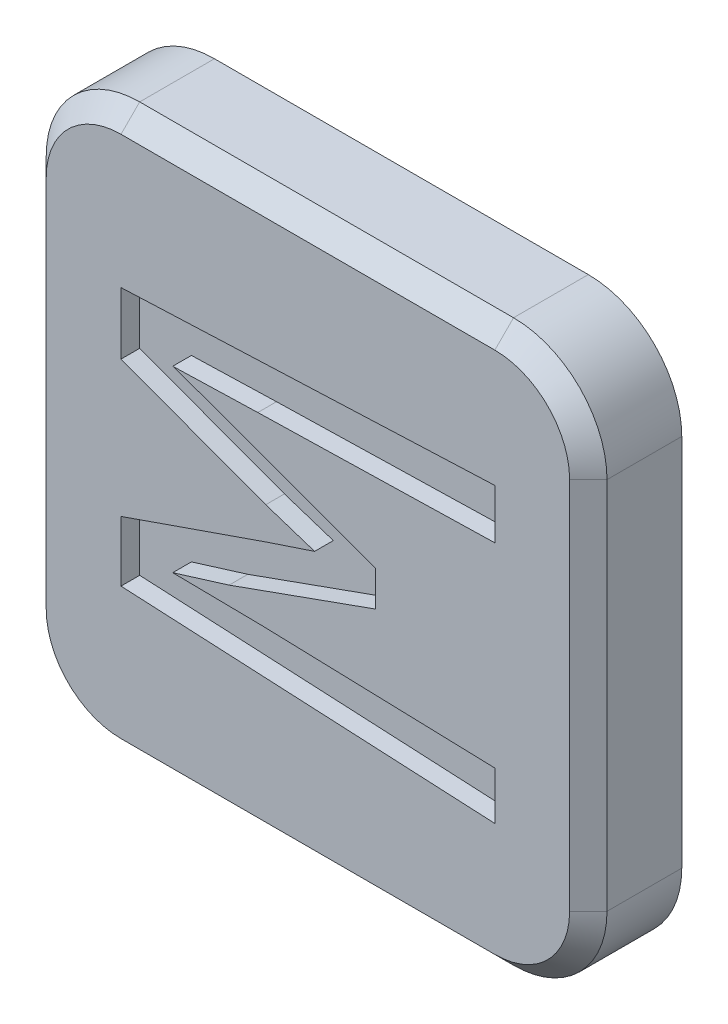
SolidWorks part; units mm, degrees
ref_plane "Front Plane" through (0, 0, 0) normal (1, 0, 0) x (0, 1, 0)
ref_plane "Top Plane" through (0, 0, 0) normal (0, 0, 1) x (0, 1, 0)
ref_plane "Right Plane" through (0, 0, 0) normal (0, 1, 0) x (-1, 0, 0)
sketch "Sketch1" plane through (0, 0, 0) normal (0, 0, 1) x (0, 1, 0)
  line L0 (-10, -10) -> (10, -10) construction
  line L1 (15, -15) -> (-15, -15)
  line L2 (15, -15) -> (15, 15)
  line L3 (15, 15) -> (-15, 15)
  line L4 (-15, -15) -> (-15, 15)
  line L5 (15, -15) -> (-15, 15) construction
  line L6 (15, 15) -> (-15, -15) construction
  text T0 "M" font "Consolas" height 20
  point P0 (0, 0)
  point P8 (0, -10)
  dimension "D1" = 30
  dimension "D2" = 30
  dimension "D3" = 20
  dimension "D4" = 10
extrude "Boss-Extrude1" add sketch "Sketch1" against normal blind 5 contours L4 L3 L2 L1
extrude "Cut-Extrude1" cut sketch "Sketch1<3>" against normal blind 1 from surface flip side to cut starting at face at (0, 0, 0)
sketch "Sketch1<3>" plane through (0, 0, 0) normal (0, 0, 1) x (0, 1, 0) same geometry as "Sketch1"
fillet "Fillet1" radius 5 4 edges at (-15, 15, -2.5) (15, 15, -2.5) (15, -15, -2.5) (-15, -15, -2.5)
chamfer "Chamfer1" distance 1 angle 45 8 edges at (15, 0, 0) (13.5355, 13.5355, 0) (13.5355, -13.5355, 0) (0, 15, 0) (0, -15, 0) (-13.5355, 13.5355, 0) (-13.5355, -13.5355, 0) (-15, 0, 0)
